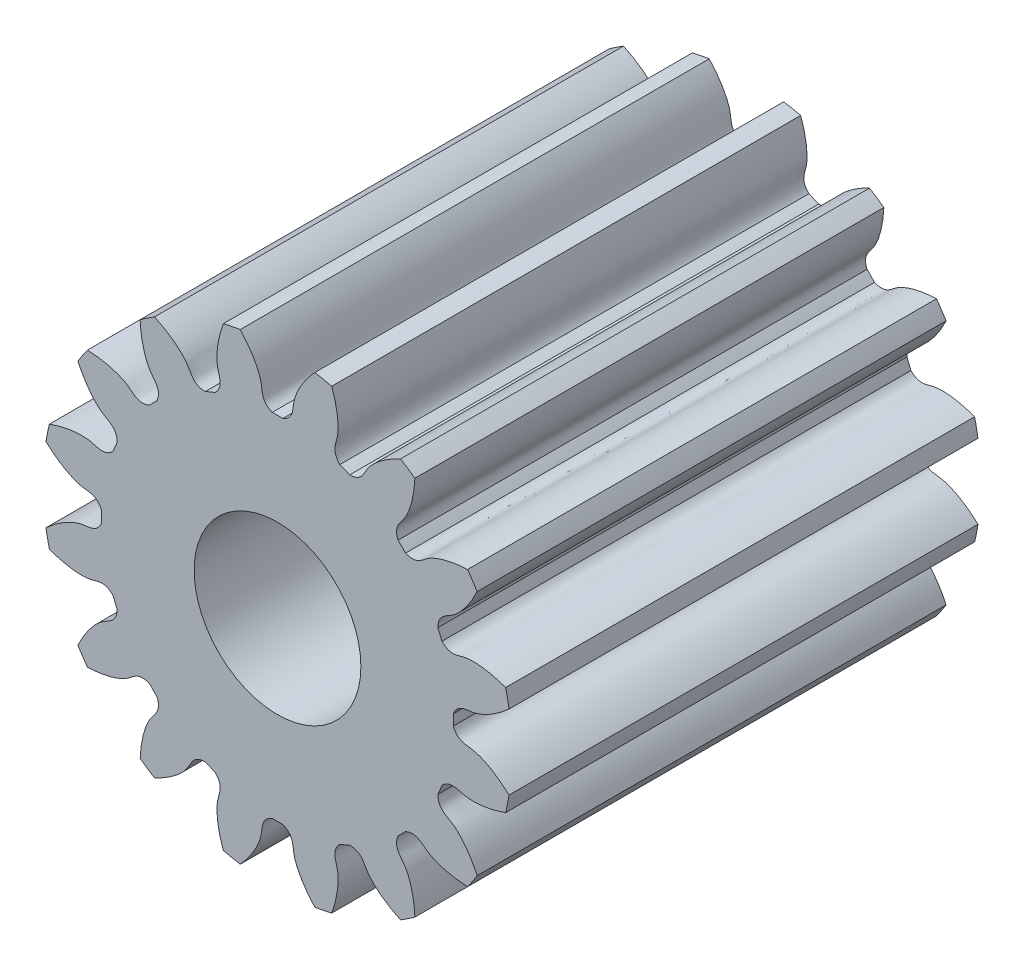
SolidWorks part; units mm, degrees
ref_plane "前视基准面" through (0, 0, 0) normal (0, 0, 1) x (1, 0, 0)
ref_plane "上视基准面" through (0, 0, 0) normal (0, 1, 0) x (1, 0, 0)
ref_plane "右视基准面" through (0, 0, 0) normal (1, 0, 0) x (0, 0, -1)
other "Configuration Table"
sketch "草图1" plane through (0, 0, 0) normal (0, 0, 1) x (1, 0, 0)
  circle A0 centre (0, 0) radius 4.5
extrude "凸台-拉伸1" add sketch "草图1" along normal blind 9
ref_axis "基准轴1" through (0, 0, 9) along (0, 0, -1)
sketch "草图2" plane through (0, 0, 0) normal (0, 0, 1) x (1, 0, 0)
  line L0 (0, 0) -> (0, 4.5) construction
  circle A0 centre (0, 0) radius 4.5 construction
  arc A1 (0.1017, 3.3735) -> (-0.1017, 3.3735) centre (0, 0) ccw
  arc A2 (1.5609, 5.0814) -> (-1.5609, 5.0814) centre (0, 0) ccw
  spline S0 degree 3 poles (0.1017, 3.3735) (0.3209, 3.4651) (0.2847, 3.6353) (0.3224, 3.7934) (0.3256, 3.8058) (0.3295, 3.8195) (0.334, 3.8346) (0.3394, 3.8511) (0.3455, 3.8688) (0.3526, 3.8879) (0.3605, 3.9082) (0.3695, 3.9297) (0.3794, 3.9524) (0.3905, 3.9763) (0.4027, 4.0013) (0.4161, 4.0274) (0.4307, 4.0545) (0.4466, 4.0827) (0.4638, 4.1118) (0.4823, 4.1419) (0.5023, 4.1728) (0.5238, 4.2046) (0.5467, 4.2372) (0.5712, 4.2705) (0.5973, 4.3045) (0.6249, 4.3392) (0.6543, 4.3744) (0.6853, 4.4102) (0.718, 4.4465) (0.7524, 4.4833) (0.7887, 4.5204) (0.8267, 4.5578) (0.8666, 4.5955) (0.9084, 4.6334) (0.952, 4.6715) (0.9975, 4.7096) (1.045, 4.7478) (1.0944, 4.7859) (1.1457, 4.8239) (1.1991, 4.8618) (1.2544, 4.8994) (1.3117, 4.9367) (1.3711, 4.9737) (1.4537, 5.023) (1.5175, 5.0584) (1.5609, 5.0814) knots 0 0 0 0 0.200958 0.205848 0.21139 0.217584 0.224431 0.231929 0.240079 0.248881 0.258335 0.268441 0.2792 0.29061 0.302672 0.315386 0.328753 0.342771 0.357441 0.372764 0.388738 0.405364 0.422643 0.440573 0.459155 0.47839 0.498276 0.518814 0.540005 0.561847 0.584342 0.607488 0.631287 0.655737 0.68084 0.706594 0.733001 0.760059 0.78777 0.816132 0.845147 0.874814 0.905132 0.936103 1 1 1 1
  spline S1 degree 3 poles (-0.1017, 3.3735) (-0.3209, 3.4651) (-0.2847, 3.6353) (-0.3224, 3.7934) (-0.3256, 3.8058) (-0.3295, 3.8195) (-0.334, 3.8346) (-0.3394, 3.8511) (-0.3455, 3.8688) (-0.3526, 3.8879) (-0.3605, 3.9082) (-0.3695, 3.9297) (-0.3794, 3.9524) (-0.3905, 3.9763) (-0.4027, 4.0013) (-0.4161, 4.0274) (-0.4307, 4.0545) (-0.4466, 4.0827) (-0.4638, 4.1118) (-0.4823, 4.1419) (-0.5023, 4.1728) (-0.5238, 4.2046) (-0.5467, 4.2372) (-0.5712, 4.2705) (-0.5973, 4.3045) (-0.6249, 4.3392) (-0.6543, 4.3744) (-0.6853, 4.4102) (-0.718, 4.4465) (-0.7524, 4.4833) (-0.7887, 4.5204) (-0.8267, 4.5578) (-0.8666, 4.5955) (-0.9084, 4.6334) (-0.952, 4.6715) (-0.9975, 4.7096) (-1.045, 4.7478) (-1.0944, 4.7859) (-1.1457, 4.8239) (-1.1991, 4.8618) (-1.2544, 4.8994) (-1.3117, 4.9367) (-1.3711, 4.9737) (-1.4537, 5.023) (-1.5175, 5.0584) (-1.5609, 5.0814) knots 0 0 0 0 0.200958 0.205848 0.21139 0.217584 0.224431 0.231929 0.240079 0.248881 0.258335 0.268441 0.2792 0.29061 0.302672 0.315386 0.328753 0.342771 0.357441 0.372764 0.388738 0.405364 0.422643 0.440573 0.459155 0.47839 0.498276 0.518814 0.540005 0.561847 0.584342 0.607488 0.631287 0.655737 0.68084 0.706594 0.733001 0.760059 0.78777 0.816132 0.845147 0.874814 0.905132 0.936103 1 1 1 1
extrude "切除-拉伸1" cut sketch "草图2" along normal through all
pattern_circular "阵列(圆周)1" count 16 every 22.5 about axis through (0, 0, 9) along (0, 0, -1) of "切除-拉伸1"
sketch "草图3" plane through (0, 0, 0) normal (0, 0, 1) x (1, 0, 0)
  circle A0 centre (0, 0) radius 4 construction
  dimension "Dn" = 8
sketch "草图4" plane through (0, 0, 9) normal (0, 0, 1) x (1, 0, 0)
  circle A0 centre (0, 0) radius 1.6
  dimension "D1" = 3.2
extrude "切除-拉伸2" cut sketch "草图4" against normal blind 10
